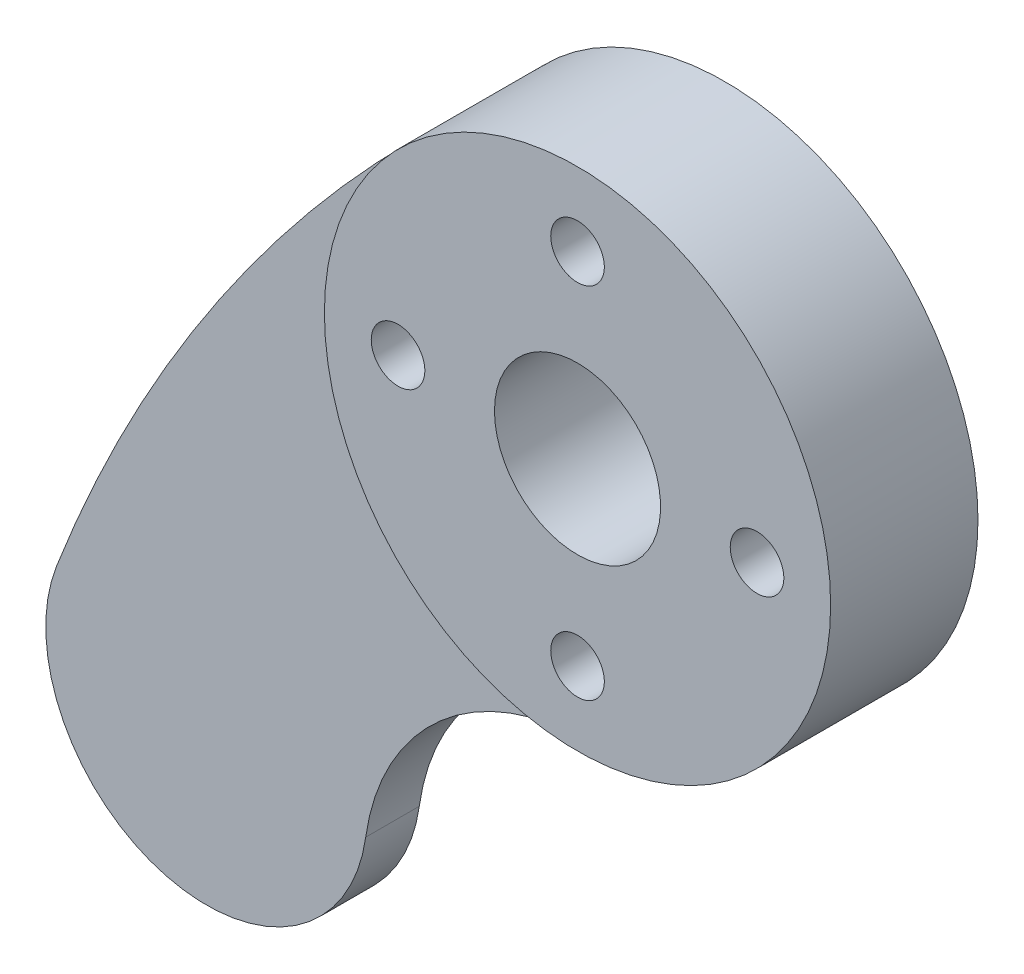
SolidWorks part; units mm, degrees
ref_plane "Front Plane" through (0, 0, 0) normal (0, 0, 1) x (1, 0, 0)
ref_plane "Top Plane" through (0, 0, 0) normal (0, 1, 0) x (1, 0, 0)
ref_plane "Right Plane" through (0, 0, 0) normal (1, 0, 0) x (0, 0, -1)
sketch "Sketch1" plane through (0, 0, 0) normal (0, 0, 1) x (1, 0, 0)
  line L0 (70.1254, 27.305) -> (58.42, 27.305) construction
  line L1 (58.42, 27.305) -> (58.42, 0) construction
  line L2 (58.42, 0) -> (99.06, 0) construction
  line L3 (99.06, 0) -> (99.06, 31.75) construction
  line L4 (99.06, 31.75) -> (73.66, 31.75) construction
  line L5 (73.66, 31.75) -> (73.66, 28.6195) construction
  line L6 (78.6801, 26.924) -> (87.4395, 26.924) construction
  line L7 (87.4395, 26.924) -> (87.4395, 24.13) construction
  line L8 (87.4395, 24.13) -> (80.9328, 22.479) construction
  line L9 (70.1254, 27.305) -> (58.42, 27.305)
  line L10 (58.42, 27.305) -> (58.42, 0)
  line L11 (58.42, 0) -> (99.06, 0)
  line L12 (99.06, 0) -> (99.06, 31.75)
  line L13 (99.06, 31.75) -> (73.66, 31.75)
  line L14 (73.66, 31.75) -> (73.66, 28.6195)
  line L15 (78.6801, 26.924) -> (87.4395, 26.924)
  line L16 (87.4395, 26.924) -> (87.4395, 24.13)
  line L17 (87.4395, 24.13) -> (80.9328, 22.479)
  line L18 (80.8812, 20.7957) -> (87.5941, 20.7957)
  line L19 (87.5941, 20.7957) -> (88.2812, 23.5039)
  line L20 (88.2812, 23.5039) -> (79.7909, 25.6582)
  line L21 (80.9328, 22.479) -> (87.4395, 26.924) construction
  line L22 (88.2812, 23.5039) -> (80.8812, 20.7957) construction
  line L23 (87.5941, 20.7957) -> (79.7909, 25.6582) construction
  line L24 (78.6801, 26.924) -> (87.4395, 24.13) construction
  line L25 (81.3178, 26.0826) -> (111.6739, 61.618) construction
  arc A0 (78.6801, 26.924) -> (73.66, 28.6195) centre (74.168, 21.844) ccw construction
  arc A1 (70.1254, 27.305) -> (80.9328, 22.479) centre (74.168, 21.844) ccw construction
  circle A2 centre (104.4893, 52.0065) radius 12 construction
  arc A3 (78.6801, 26.924) -> (73.66, 28.6195) centre (74.168, 21.844) ccw
  arc A4 (70.1254, 27.305) -> (80.9328, 22.479) centre (74.168, 21.844) ccw
  circle A5 centre (104.4893, 52.0065) radius 12
  circle A6 centre (56.226, 91.417) radius 74.31
  circle A7 centre (86.2672, 31.8764) radius 7.62
  circle A8 centre (148.4954, 7.8931) radius 74.31
  dimension "D2" = 15.24
  dimension "D1" = 46.736
extrude "Boss-Extrude1" add sketch "Sketch1" along normal blind 3.175 contours L13 A7 | L13 A7 L15 L16 | L15 A7 L16 | A7 A6 L12 L13 | A5 A8 A7 L13 L12 A6 | A5 region at (94.0508, 41.3164, 0) region at (104.4893, 52.0065, 0) region at (95.3834, 29.7296, 0) region at (86.5606, 29.0842, 0) region at (84.6642, 25.7868, 0) region at (86.2672, 35.0423, 0)
sketch "Sketch2" plane through (0, 0, 0) normal (0, 0, -1) x (-1, 0, 0)
  circle A0 centre (-104.4893, 52.0065) radius 12
extrude "Boss-Extrude2" add sketch "Sketch2" along normal blind 3.81
sketch "Sketch3" plane through (0, 0, -3.81) normal (0, 0, -1) x (-1, 0, 0)
  circle A1 centre (-104.4893, 52.0065) radius 12
  circle A2 centre (-104.4893, 52.0065) radius 12
  circle A4 centre (-104.4893, 52.0065) radius 3.937
  dimension "D2" = 7.874
  dimension "D1" = 0
extrude "Cut-Extrude1" cut sketch "Sketch3" against normal through all contours A4
sketch "Sketch4" plane through (0, 0, -3.81) normal (0, 0, -1) x (-1, 0, 0)
  line L0 (-104.4893, 60.5155) -> (-104.4893, 52.0065) construction
  line L1 (-104.4893, 52.0065) -> (-104.4893, 43.4975) construction
  line L2 (-104.4893, 52.0065) -> (-95.9803, 52.0065) construction
  line L3 (-104.4893, 52.0065) -> (-112.9983, 52.0065) construction
  circle A1 centre (-104.4893, 52.0065) radius 12
  circle A2 centre (-104.4893, 52.0065) radius 12
  circle A5 centre (-104.4893, 52.0065) radius 8.509 construction
  circle A6 centre (-95.9803, 52.0065) radius 1.27
  circle A7 centre (-112.9983, 52.0065) radius 1.27
  circle A8 centre (-104.4893, 43.4975) radius 1.27
  circle A9 centre (-104.4893, 60.5155) radius 1.27
  dimension "D2" = 17.018
  dimension "D3" = 2.54
  dimension "D1" = 0
extrude "Cut-Extrude2" cut sketch "Sketch4" against normal through all contours A7 | A6 | A9 | A8 region at (95.9803, 52.0065, -3.81) region at (112.9983, 52.0065, -3.81)
sketch "Sketch5" plane through (0, 0, 0) normal (0, 0, -1) x (-1, 0, 0)
  arc A0 (-113.7841, 44.4166) -> (-96.0143, 60.5021) centre (-104.4893, 52.0065) ccw construction
  arc A1 (-113.7841, 44.4166) -> (-89.6997, 25.0733) centre (-56.226, 91.417) ccw construction
  arc A2 (-89.6997, 25.0733) -> (-79.157, 34.6168) centre (-86.2672, 31.8764) ccw construction
  arc A3 (-79.157, 34.6168) -> (-96.0143, 60.5021) centre (-148.4954, 7.8931) ccw construction
  circle A4 centre (-104.4893, 52.0065) radius 12 construction
  arc A5 (-113.7841, 44.4166) -> (-96.0143, 60.5021) centre (-104.4893, 52.0065) ccw
  arc A6 (-113.7841, 44.4166) -> (-89.6997, 25.0733) centre (-56.226, 91.417) ccw
  arc A7 (-89.6997, 25.0733) -> (-79.157, 34.6168) centre (-86.2672, 31.8764) ccw
  arc A8 (-79.157, 34.6168) -> (-96.0143, 60.5021) centre (-148.4954, 7.8931) ccw
  circle A9 centre (-104.4893, 52.0065) radius 12
  circle A10 centre (-86.2672, 31.8764) radius 7.62
  circle A11 centre (-104.4893, 52.0065) radius 12
  arc A12 (-93.8135, 30.8191) -> (-104.4305, 40.0066) centre (-104.3783, 29.3388) ccw
  arc M2 (-113.7841, 44.4166) -> (-89.6997, 25.0733) centre (-56.226, 91.417) ccw
  dimension "D1" = 10.668
extrude "Cut-Extrude3" cut sketch "Sketch5" against normal through all contours A10 A12 A11 M2 region at (100.4293, 35.0094, 0)
sketch "Sketch6" plane through (0, 0, 3.175) normal (0, 0, 1) x (1, 0, 0)
  arc A4 (79.157, 34.6168) -> (93.8135, 30.8191) centre (86.2672, 31.8764) ccw
  arc A5 (104.4305, 40.0066) -> (93.8135, 30.8191) centre (104.3783, 29.3388) ccw
  arc A6 (104.4305, 40.0066) -> (96.0143, 60.5021) centre (104.4893, 52.0065) ccw
  arc A7 (96.0143, 60.5021) -> (79.157, 34.6168) centre (148.4954, 7.8931) ccw
  arc A8 (79.157, 34.6168) -> (93.8135, 30.8191) centre (86.2672, 31.8764) ccw
  arc A9 (104.4305, 40.0066) -> (93.8135, 30.8191) centre (104.3783, 29.3388) ccw
  arc A10 (104.4305, 40.0066) -> (96.0143, 60.5021) centre (104.4893, 52.0065) ccw
  arc A11 (96.0143, 60.5021) -> (79.157, 34.6168) centre (148.4954, 7.8931) ccw
  circle A20 centre (104.4893, 52.0065) radius 12
  arc M10 (79.157, 34.6168) -> (93.8135, 30.8191) centre (86.2672, 31.8764) ccw
  arc M11 (93.8135, 30.8191) -> (104.4305, 40.0066) centre (104.3783, 29.3388) cw
  arc M13 (96.0143, 60.5021) -> (79.157, 34.6168) centre (148.4954, 7.8931) ccw
  dimension "D1" = 0
extrude "Cut-Extrude4" cut sketch "Sketch6" against normal blind 0.635 contours A20 M13 M10 M11 region at (88.5334, 37.6679, 3.175)
